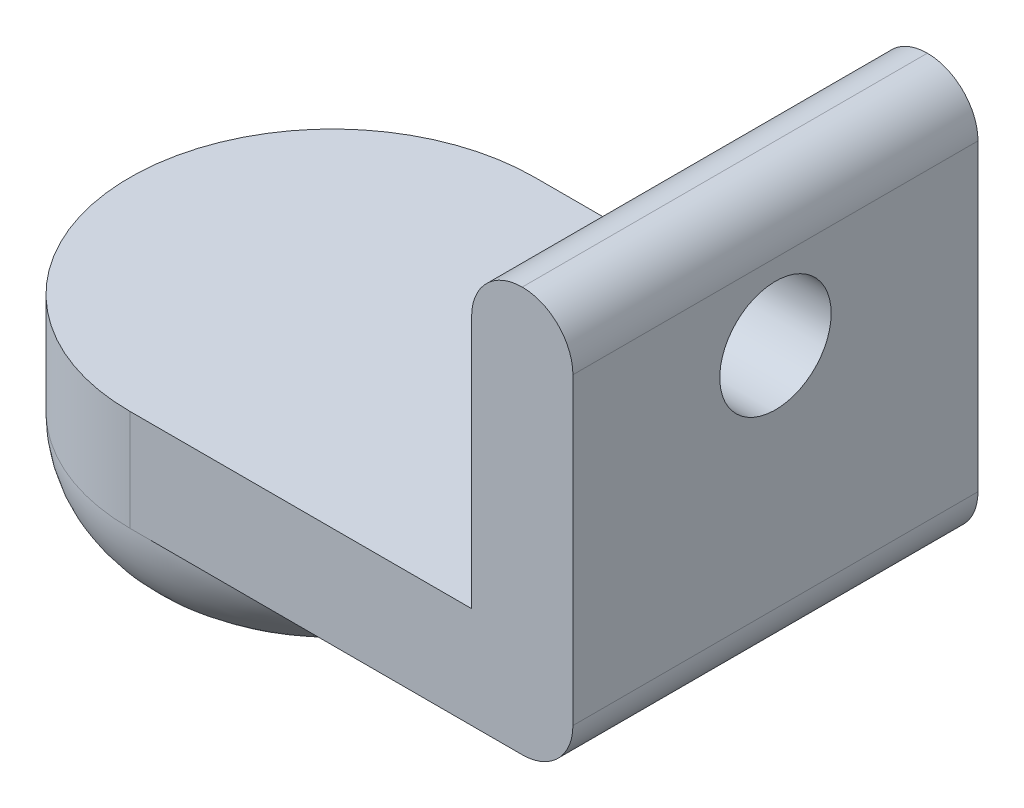
SolidWorks part; units mm, degrees
ref_plane "前视基准面" through (0, 0, 0) normal (0, 0, 1) x (1, 0, 0)
ref_plane "上视基准面" through (0, 0, 0) normal (0, 1, 0) x (1, 0, 0)
ref_plane "右视基准面" through (0, 0, 0) normal (1, 0, 0) x (0, 0, -1)
other "Configuration Table"
sketch "草图1" plane through (0, 0, 0) normal (0, 1, 0) x (1, 0, 0)
  line L0 (0, 0) -> (25.75, 0) construction
  line L1 (0, 4) -> (25.75, 4)
  line L2 (0, -4) -> (25.75, -4)
  line L3 (0, 4) -> (25.75, 4) construction
  line L4 (25.75, 4) -> (25.75, -4)
  arc A0 (0, 4) -> (0, -4) centre (0, 0) ccw
  circle A2 centre (0, 0) radius 2.525
  dimension "D1" = 5.05
  dimension "D2" = 4
  dimension "D4" = 90
  dimension "D3" = 8
  dimension "D5" = 25.75
  dimension "D6" = 25.75
  dimension "D7" = 4
extrude "凸台-拉伸1" add sketch "草图1" along normal blind 2
sketch "草图2" plane through (0, 2, 0) normal (0, 1, 0) x (1, 0, 0)
  circle A0 centre (0, 0) radius 2.525 construction
  circle A1 centre (0, 0) radius 2.525
extrude "凸台-拉伸2" add sketch "草图2" against normal up to surface (2 mm away) up to face at (11.875, 0, 0)
sketch "草图3" plane through (0, 0, 0) normal (0, 1, 0) x (1, 0, 0)
  circle A0 centre (0, 0) radius 4
  dimension "D1" = 8
extrude "凸台-拉伸3" add sketch "草图3" against normal blind 2
fillet "圆角2" radius 2 1 edges at (0, -2, 4)
sketch "草图10" plane through (0, 0, -4) normal (0, 0, -1) x (-1, 0, 0)
  line L0 (-25.75, 2) -> (-25.75, 4)
  line L2 (-22.75, 4) -> (-22.75, 2)
  line L3 (-25.75, 2) -> (0, 2) construction
  line L4 (-25.75, 2) -> (-22.75, 2)
  line L5 (-22.75, 2) -> (-18.75, 2) construction
  line L6 (-18.75, 2) -> (-15.75, 2)
  line L7 (-15.75, 2) -> (-15.75, 4)
  line L9 (-18.75, 4) -> (-18.75, 2)
  arc A0 (-22.75, 4) -> (-25.75, 4) centre (-24.25, 4) ccw
  arc A1 (-15.75, 4) -> (-18.75, 4) centre (-17.25, 4) ccw
  dimension "D3" = 4
  dimension "D7" = 1.5
  dimension "D8" = 1.5
  dimension "D1" = 2
  dimension "D2" = 3
  dimension "D4" = 3
  dimension "D5" = 2
  dimension "D6" = 3
  dimension "D9" = 18.75
extrude "凸台-拉伸6" add sketch "草图10" against normal up to surface (8 mm away) up to face at (12.875, 1, 4)
sketch "草图11" plane through (0, 0, -4) normal (0, 0, -1) x (-1, 0, 0)
  circle A2 centre (-17.25, 4) radius 1.05
  circle A3 centre (-24.25, 4) radius 1.05
  dimension "D2" = 2.1
  dimension "D3" = 2.1
extrude "切除-拉伸1" cut sketch "草图11" against normal through all
fillet "圆角3" radius 1 1 edges at (25.75, 0, 0)
sketch "草图12" plane through (25.75, 0, 0) normal (1, 0, 0) x (0, 0, -1)
  line L0 (-4, 5.5) -> (-4, 0)
  line L1 (-4, 0) -> (4, 0)
  line L2 (4, 0) -> (4, 1) construction
  line L3 (4, 0) -> (4, 5.5)
  line L4 (4, 4) -> (4, 5.5) construction
  line L5 (4, 5.5) -> (-4, 5.5)
extrude "切除-拉伸2" cut sketch "草图12" against normal blind 17
sketch "草图13" plane through (0, 2, 0) normal (0, 1, 0) x (1, 0, 0)
  line L0 (8.75, 4) -> (6.75, 4)
  line L1 (8.75, 4) -> (0, 4) construction
  line L2 (6.75, 4) -> (6.75, -4)
  line L3 (0, -4) -> (8.75, -4) construction
  line L4 (6.75, -4) -> (8.75, -4)
  line L5 (8.75, -4) -> (8.75, 4)
  dimension "D1" = 2
extrude "凸台-拉伸7" add sketch "草图13" along normal blind 6
fillet "圆角4" radius 1 1 edges at (8.75, 0, 0)
fillet "圆角5" radius 1 2 edges at (6.75, 8, 0) (8.75, 8, 0)
sketch "草图14" plane through (8.75, 0, 0) normal (1, 0, 0) x (0, 0, -1)
  line L0 (0, 8) -> (0, 5.5) construction
  line L2 (-4, 8) -> (4, 8) construction
  circle A0 centre (0, 5.5) radius 1.1
  dimension "D2" = 2.2
  dimension "D1" = 2.5
extrude "切除-拉伸3" cut sketch "草图14" against normal blind 10
